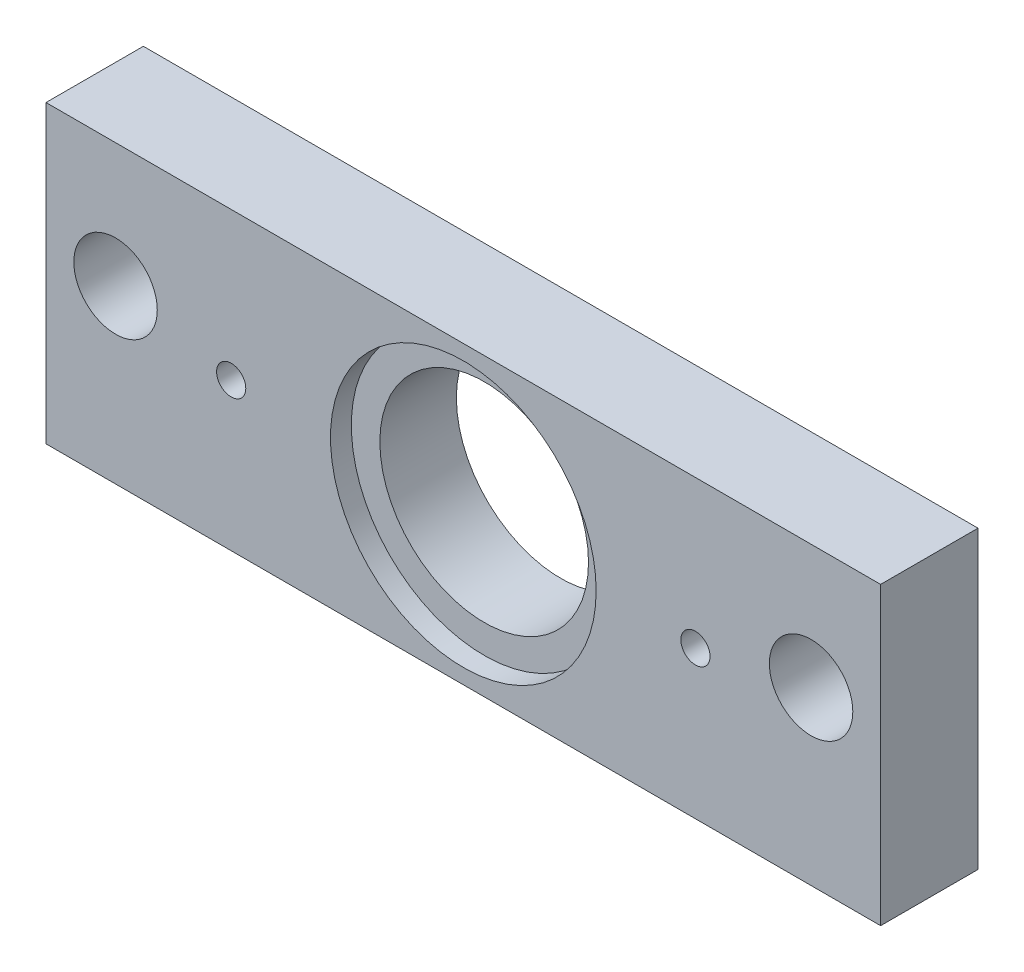
SolidWorks part; units mm, degrees
ref_plane "Front Plane" through (0, 0, 0) normal (0, 0, 1) x (1, 0, 0)
ref_plane "Top Plane" through (0, 0, 0) normal (0, 1, 0) x (1, 0, 0)
ref_plane "Right Plane" through (0, 0, 0) normal (1, 0, 0) x (0, 0, -1)
sketch "Sketch1" plane through (0, 0, 0) normal (0, 0, 1) x (1, 0, 0)
  line L1 (-60, -21.25) -> (60, -21.25)
  line L2 (-60, -21.25) -> (-60, 21.25)
  line L3 (-60, 21.25) -> (60, 21.25)
  line L4 (60, -21.25) -> (60, 21.25)
  line L5 (-60, -21.25) -> (60, 21.25) construction
  line L6 (-60, 21.25) -> (60, -21.25) construction
  point P0 (0, 0)
  dimension "D1" = 120
  dimension "D2" = 42.5
extrude "Boss-Extrude1" add sketch "Sketch1" along normal mid plane 14
sketch "Sketch2" plane through (0, 0, 7) normal (0, 0, 1) x (1, 0, 0)
  circle A0 centre (0, 0) radius 19.1
  dimension "D1" = 38.2
extrude "Cut-Extrude1" cut sketch "Sketch2" against normal blind 3
sketch "Sketch3" plane through (0, 0, 4) normal (0, 0, 1) x (1, 0, 0)
  circle A0 centre (0, 0) radius 15
extrude "Cut-Extrude2" cut sketch "Sketch3" against normal through all
sketch "Sketch4" plane through (0, 0, 7) normal (0, 0, 1) x (1, 0, 0)
  circle A0 centre (-33.375, 0) radius 2.1
  circle A1 centre (33.375, 0) radius 2.1
  dimension "D1" = 4.2
  dimension "D2" = 4.2
  dimension "D3" = 33.375
  dimension "D4" = 33.375
extrude "Cut-Extrude3" cut sketch "Sketch4" against normal through all
sketch "Sketch5" plane through (0, 0, 7) normal (0, 0, 1) x (1, 0, 0)
  line L0 (-40.6477, 3.4) -> (36.4799, 3.4) construction
  circle A0 centre (-50, 3.4) radius 6
  circle A1 centre (50, 3.4) radius 6
  dimension "D1" = 12
  dimension "D2" = 12
  dimension "D4" = 50
  dimension "D3" = 50
  dimension "D5" = 3.4
extrude "Cut-Extrude4" cut sketch "Sketch5" against normal through all
sketch "Sketch6" plane through (0, -21.25, 0) normal (0, -1, 0) x (1, 0, 0)
  line L0 (-60, 0) -> (60, 0) construction
  line L1 (-60, 7) -> (-60, -7) construction
  line L2 (60, 7) -> (60, -7) construction
  circle A0 centre (-50, 0) radius 2.1
  circle A1 centre (-25, 0) radius 2.1
  circle A2 centre (25, 0) radius 2.1
  circle A3 centre (50, 0) radius 2.1
  circle A4 centre (-37.5, 0) radius 1.25
  circle A5 centre (37.5, 0) radius 1.25
  dimension "D1" = 4.2
  dimension "D2" = 4.2
  dimension "D3" = 4.2
  dimension "D4" = 4.2
  dimension "D5" = 10
  dimension "D9" = 2.5
  dimension "D10" = 2.5
  dimension "D11" = 22.5
  dimension "D12" = 22.5
  dimension "D6" = 35
  dimension "D7" = 10
  dimension "D8" = 35
extrude "Cut-Extrude5" cut sketch "Sketch6" against normal blind 10
equation "\"D4@Sketch4\"=\"D3@Sketch4\""
